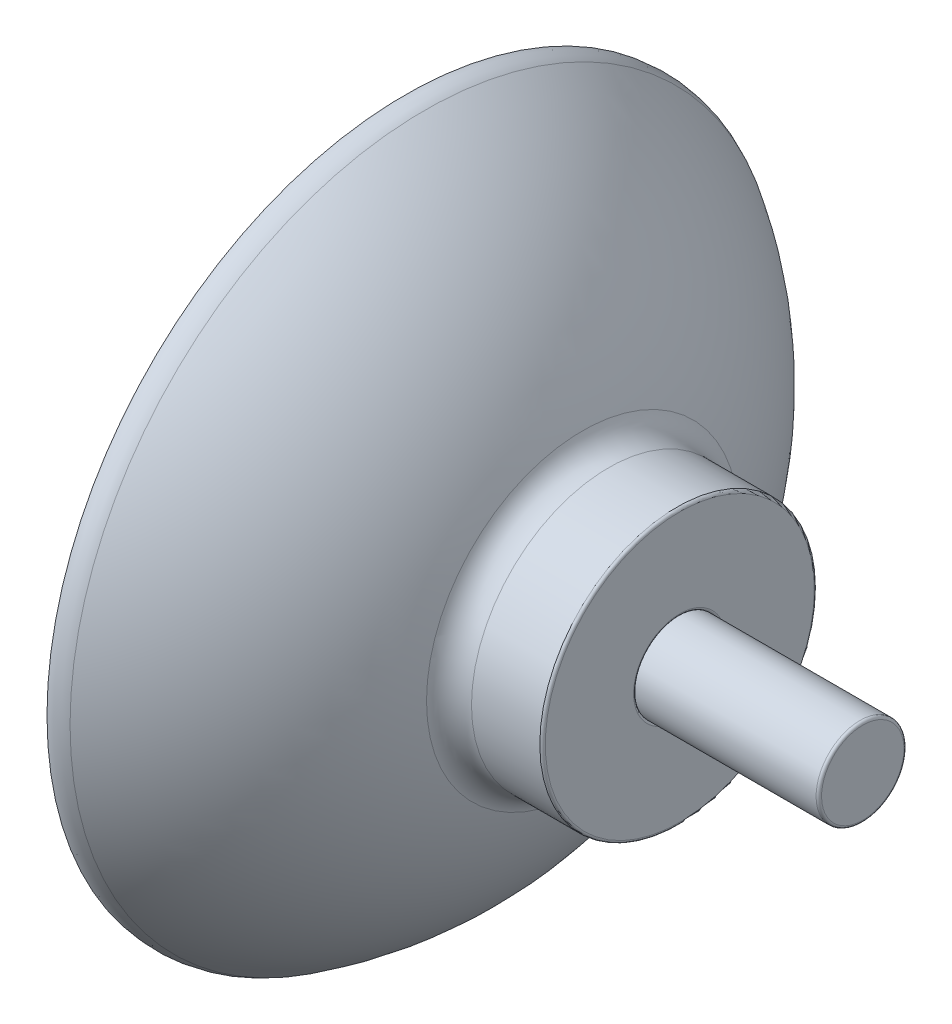
SolidWorks part; units mm, degrees
ref_plane "Płaszczyzna przednia" through (0, 0, 0) normal (0, 0, 1) x (1, 0, 0)
ref_plane "Płaszczyzna górna" through (0, 0, 0) normal (0, 1, 0) x (1, 0, 0)
ref_plane "Płaszczyzna prawa" through (0, 0, 0) normal (1, 0, 0) x (0, 0, -1)
sketch "Szkic1" plane through (0, 0, 0) normal (0, 1, 0) x (1, 0, 0)
  line L0 (0, 0) -> (-10, 0) construction
  line L1 (0, 0) -> (5, 0) construction
  line L2 (0, 0) -> (0, 7.5)
  line L3 (0, 7.5) -> (5, 7.5)
  line L4 (5, 0) -> (5, 7.5)
  line L5 (2, 0) -> (4, 0) construction
  line L6 (2, 0) -> (2, 4.75)
  line L7 (2, 4.75) -> (4, 4.75)
  line L8 (4, 0) -> (4, 4.75)
  line L9 (-10, 0) -> (-10, 20) construction
  line L10 (-10, 20) -> (-10, 19.5)
  line L11 (5, 0) -> (4, 0)
  line L12 (4, 0) -> (2, 0)
  line L13 (2, 0) -> (0, 0)
  line L14 (4, 2.375) -> (5, 2.375)
  arc A0 (-10, 20) -> (0, 7.5) centre (-19.3122, 2.3002) cw
  arc A1 (-10, 19.5) -> (0, 4) centre (-21.7836, 0.9219) cw
  dimension "D8" = 20
  dimension "D11" = 22
  dimension "D1" = 5
  dimension "D2" = 7.5
  dimension "D3" = 2
  dimension "D4" = 4.75
  dimension "D5" = 1
  dimension "D6" = 20
  dimension "D7" = 10
  dimension "D9" = 0.5
  dimension "D10" = 3.5
revolve "Obrót1" add sketch "Szkic1" angle 360 about L0 region at (0.0901, 0, -2) region at (-3.1385, 0, -12.951)
fillet "Zaokrąglenie1" radius 0.15 5 edges at (4, 0, -2.375) (5, 0, -2.375) (5, 0, -7.5) (-10, 0, -19.5) (0, 0, -4)
fillet "Zaokrąglenie2" radius 1.5 2 edges at (-10, 0, -20) (0, 0, -7.5)
sketch "Szkic2" plane through (0, 0, 0) normal (0, 0, 1) x (1, 0, 0)
  line L0 (2, 0) -> (2, 4.75)
  line L1 (2, -4.75) -> (2, 4.75) construction
  line L2 (2, 4.75) -> (4, 4.75)
  line L3 (4, 4.75) -> (4, -4.75) construction
  line L4 (4, 4.75) -> (4, 2.4)
  line L5 (4, 2.4) -> (15, 2.4)
  line L6 (15, 2.4) -> (15, 0)
  line L7 (15, 0) -> (2, 0)
  line L8 (5, -7.35) -> (5, 7.35) construction
  point P4 (15, 1.2)
  dimension "D1" = 10
  dimension "D2" = 2.35
  dimension "D3" = 2.4
revolve "Obrót2" add sketch "Szkic2" angle 360 about L7
fillet "Zaokrąglenie3" radius 0.15 1 edges at (15, 2.4, 0)
